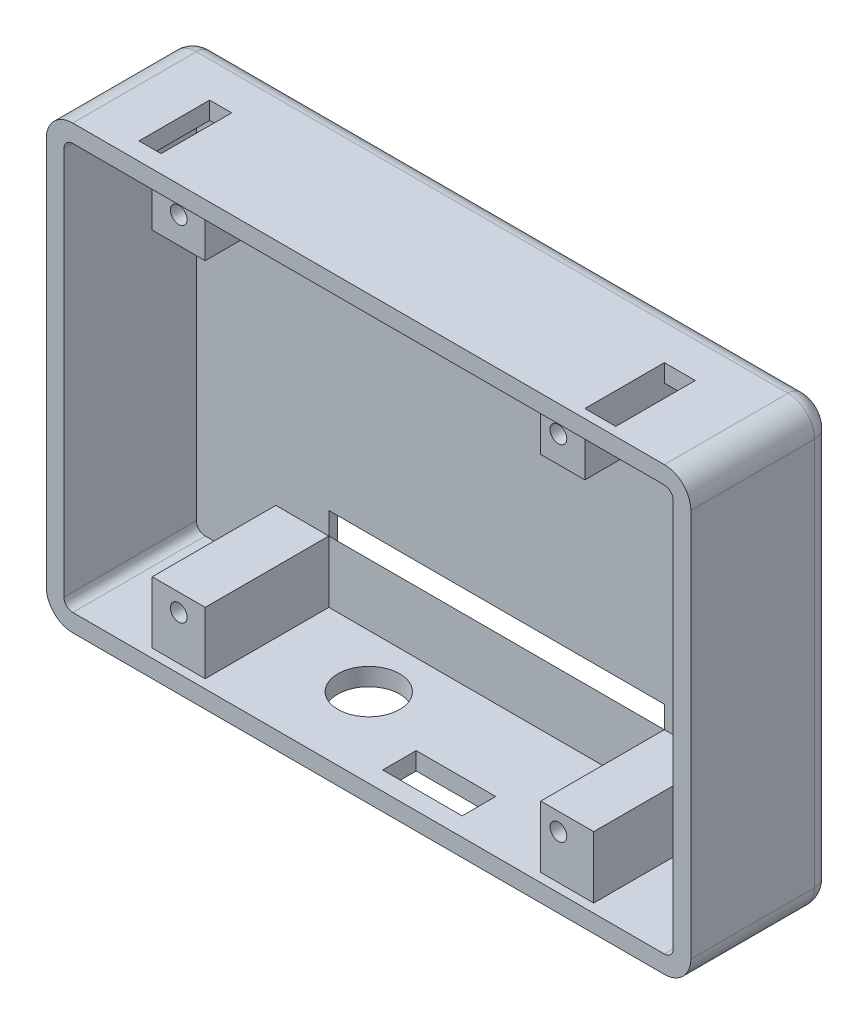
SolidWorks part; units mm, degrees
ref_plane "Front Plane" through (0, 0, 0) normal (0, 0, 1) x (1, 0, 0)
ref_plane "Top Plane" through (0, 0, 0) normal (0, 1, 0) x (1, 0, 0)
ref_plane "Right Plane" through (0, 0, 0) normal (1, 0, 0) x (0, 0, -1)
sketch "Sketch1" plane through (0, 0, 0) normal (0, 0, 1) x (1, 0, 0)
  line L1 (-36.5, -25) -> (36.5, -25)
  line L2 (-36.5, -25) -> (-36.5, 25)
  line L3 (-36.5, 25) -> (36.5, 25)
  line L4 (36.5, -25) -> (36.5, 25)
  line L5 (-36.5, -25) -> (36.5, 25) construction
  line L6 (-36.5, 25) -> (36.5, -25) construction
  point P0 (0, 0)
  dimension "D1" = 50
  dimension "D2" = 73
extrude "Boss-Extrude1" add sketch "Sketch1" along normal blind 1
sketch "Sketch2" plane through (0, 0, 1) normal (0, 0, 1) x (1, 0, 0)
  line L1 (-36.5, -25) -> (36.5, -25)
  line L2 (-36.5, -25) -> (-36.5, 25)
  line L3 (-36.5, 25) -> (36.5, 25)
  line L4 (36.5, -25) -> (36.5, 25)
  line L5 (-36.5, -25) -> (36.5, 25) construction
  line L6 (-36.5, 25) -> (36.5, -25) construction
  line L7 (-34.5, -23) -> (34.5, -23)
  line L8 (-34.5, -23) -> (-34.5, 23)
  line L9 (-34.5, 23) -> (34.5, 23)
  line L10 (34.5, -23) -> (34.5, 23)
  line L11 (-34.5, -23) -> (34.5, 23) construction
  line L12 (-34.5, 23) -> (34.5, -23) construction
  point P0 (0, 0)
  point P7 (0, 0)
  dimension "D1" = 2
  dimension "D2" = 2
extrude "Boss-Extrude2" add sketch "Sketch2" along normal blind 15
fillet "Fillet1" radius 3 4 edges at (-36.5, 25, 8) (-36.5, -25, 8) (36.5, 25, 8) (36.5, -25, 8)
fillet "Fillet2" radius 1 4 edges at (34.5, -23, 8.5) (-34.5, -23, 8.5) (-34.5, 23, 8.5) (34.5, 23, 8.5)
sketch "Sketch3" plane through (0, -25, 0) normal (0, -1, 0) x (1, 0, 0)
  line L0 (-33.5, 16) -> (33.5, 16) construction
  line L1 (-0.5, 13.9) -> (8.5, 13.9)
  line L2 (-0.5, 13.9) -> (-0.5, 10.1)
  line L3 (-0.5, 10.1) -> (8.5, 10.1)
  line L4 (8.5, 13.9) -> (8.5, 10.1)
  line L5 (7.5, 10.5) -> (7.5, 13.5) construction
  line L6 (0.5, 13.5) -> (0.5, 10.5) construction
  dimension "D1" = 2.1
  dimension "D2" = 3.8
  dimension "D3" = 1
  dimension "D4" = 1
extrude "Cut-Extrude1" cut sketch "Sketch3" against normal blind 2
sketch "Sketch5" plane through (0, -23, 0) normal (0, 1, 0) x (1, 0, 0)
  circle A0 centre (-8.9764, -7) radius 3.5
  dimension "D1" = 7
extrude "Cut-Extrude2" cut sketch "Sketch5" against normal blind 2
sketch "Sketch6" plane through (0, 0, 1) normal (0, 0, 1) x (1, 0, 0)
  line L0 (33.5, 23) -> (-33.5, 23) construction
  line L1 (-25.5, 23) -> (-19.5, 23)
  line L2 (-25.5, 23) -> (-25.5, 18)
  line L3 (-25.5, 18) -> (-19.5, 18)
  line L4 (-19.5, 23) -> (-19.5, 18)
  line L5 (34.5, -22) -> (34.5, 22) construction
  line L6 (23.5, 23) -> (18.5, 23)
  line L7 (23.5, 23) -> (23.5, 18)
  line L8 (23.5, 18) -> (18.5, 18)
  line L9 (18.5, 23) -> (18.5, 18)
  line L10 (-34.5, 22) -> (-34.5, -22) construction
  dimension "D1" = 6
  dimension "D2" = 5
  dimension "D3" = 5
  dimension "D4" = 5
  dimension "D5" = 16
  dimension "D6" = 9
extrude "Boss-Extrude3" add sketch "Sketch6" along normal blind 14
sketch "Sketch7" plane through (0, 0, 1) normal (0, 0, 1) x (1, 0, 0)
  line L0 (-33.5, -23) -> (33.5, -23) construction
  line L1 (18.5, -23) -> (24.5, -23)
  line L2 (18.5, -23) -> (18.5, -16)
  line L3 (18.5, -16) -> (24.5, -16)
  line L4 (24.5, -23) -> (24.5, -16)
  line L5 (34.5, -22) -> (34.5, 22) construction
  line L6 (-25.5, -23) -> (-19.5, -23)
  line L7 (-25.5, -23) -> (-25.5, -16)
  line L8 (-25.5, -16) -> (-19.5, -16)
  line L9 (-19.5, -23) -> (-19.5, -16)
  line L10 (-34.5, 22) -> (-34.5, -22) construction
  dimension "D1" = 10
  dimension "D2" = 6
  dimension "D3" = 9
  dimension "D4" = 7
extrude "Boss-Extrude4" add sketch "Sketch7" along normal blind 14
fillet "Fillet3" radius 2 8 edges at (35.6213, -24.1213, 0) (36.5, 0, 0) (35.6213, 24.1213, 0) (0, 25, 0) (-35.6213, 24.1213, 0) (-36.5, 0, 0) (-35.6213, -24.1213, 0) (0, -25, 0)
sketch "Sketch8" plane through (0, 23, 0) normal (0, -1, 0) x (1, 0, 0)
  line L0 (-25.5, 15) -> (-25.5, 1) construction
  line L1 (-28, 6) -> (-25.5, 6)
  line L2 (-28, 6) -> (-28, 13.9992)
  line L3 (-28, 13.9992) -> (-25.5, 13.9992)
  line L4 (-25.5, 6) -> (-25.5, 13.9992)
  line L6 (27, 6) -> (23.5, 6)
  line L7 (27, 6) -> (27, 15)
  line L8 (27, 15) -> (23.5, 15)
  line L9 (23.5, 6) -> (23.5, 15)
extrude "Cut-Extrude3" cut sketch "Sketch8" against normal through all
sketch "Sketch9" plane through (0, 0, 15) normal (0, 0, 1) x (1, 0, 0)
  circle A0 centre (-22.5, 21) radius 0.95
  circle A1 centre (20.5, 21) radius 0.95
  circle A2 centre (20.5, -18) radius 0.95
  circle A3 centre (-22.5, -18) radius 0.95
  dimension "D1" = 1.9
extrude "Cut-Extrude4" cut sketch "Sketch9" against normal through all
sketch "Sketch10" plane through (0, 0, 1) normal (0, 0, 1) x (1, 0, 0)
  line L1 (18.5, 18) -> (-19.5, 18)
  line L2 (18.5, 18) -> (18.5, 16.5)
  line L3 (18.5, 16.5) -> (-19.5, 16.5)
  line L4 (-19.5, 18) -> (-19.5, 16.5)
  line L5 (18.5, -16) -> (-19.5, -16)
  line L6 (18.5, -16) -> (18.5, -14.5)
  line L7 (18.5, -14.5) -> (-19.5, -14.5)
  line L8 (-19.5, -16) -> (-19.5, -14.5)
  dimension "D1" = 1.5
extrude "Cut-Extrude5" cut sketch "Sketch10" against normal through all
chamfer "Chamfer1" distance 1 angle 45 2 edges at (-0.5, -16, 0) (-0.5, 18, 0)
chamfer "Chamfer2" distance 1 angle 45 2 edges at (-0.5, 16.5, 1) (-0.5, -14.5, 1)
